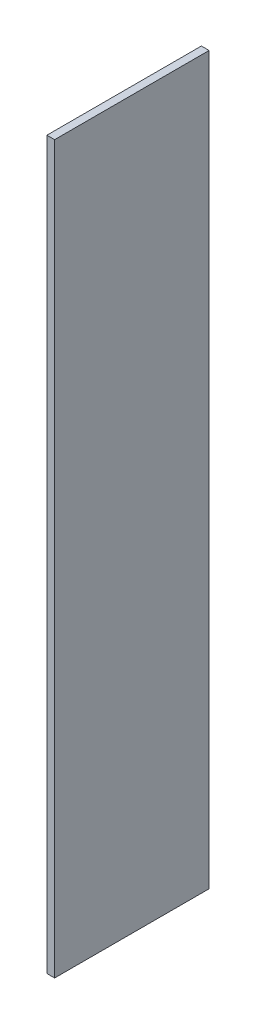
SolidWorks part; units mm, degrees
ref_plane "Front Plane" through (0, 0, 0) normal (0, 0, 1) x (1, 0, 0)
ref_plane "Top Plane" through (0, 0, 0) normal (0, 1, 0) x (1, 0, 0)
ref_plane "Right Plane" through (0, 0, 0) normal (1, 0, 0) x (0, 0, -1)
sketch "Sketch1" plane through (0, 0, 0) normal (1, 0, 0) x (0, 0, -1)
  line L1 (0, 0) -> (63.5, 0)
  line L2 (0, 0) -> (0, 298.45)
  line L3 (0, 298.45) -> (63.5, 298.45)
  line L4 (63.5, 0) -> (63.5, 298.45)
  dimension "D1" = 298.45
  dimension "D2" = 63.5
extrude "Boss-Extrude1" add sketch "Sketch1" along normal blind 3.175
